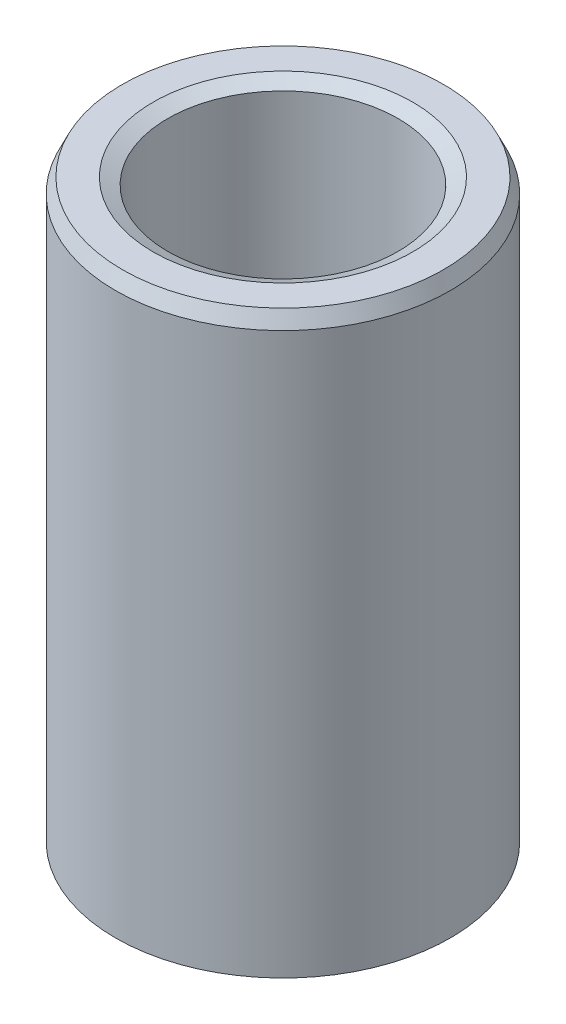
SolidWorks part; units mm, degrees
ref_plane "Front Plane" through (0, 0, 0) normal (0, 0, 1) x (1, 0, 0)
ref_plane "Top Plane" through (0, 0, 0) normal (0, 1, 0) x (1, 0, 0)
ref_plane "Right Plane" through (0, 0, 0) normal (1, 0, 0) x (0, 0, -1)
sketch "Sketch1" plane through (0, 0, 0) normal (0, 1, 0) x (1, 0, 0)
  circle A0 centre (0, 0) radius 15
  dimension "SLEEVE_OD" = 30
extrude "Boss-Extrude1" add sketch "Sketch1" along normal blind 52.159
sketch "Sketch2" plane through (0, 0, 0) normal (0, 1, 0) x (1, 0, 0)
  circle A0 centre (0, 0) radius 10.3186
  dimension "BORE_D" = 20.6372
extrude "Cut-Extrude1" cut sketch "Sketch2" along normal through all
chamfer "Chamfer1" distance 1.3109 angle 25.181 4 edges at (0, 52.159, 10.3186) (0, 0, 10.3186) (0, 0, 15) (0, 52.159, 15) first distance on face at (0, 52.159, 10.3186) first distance on face at (0, 0, 10.3186) first distance on face at (0, 52.159, 15)
